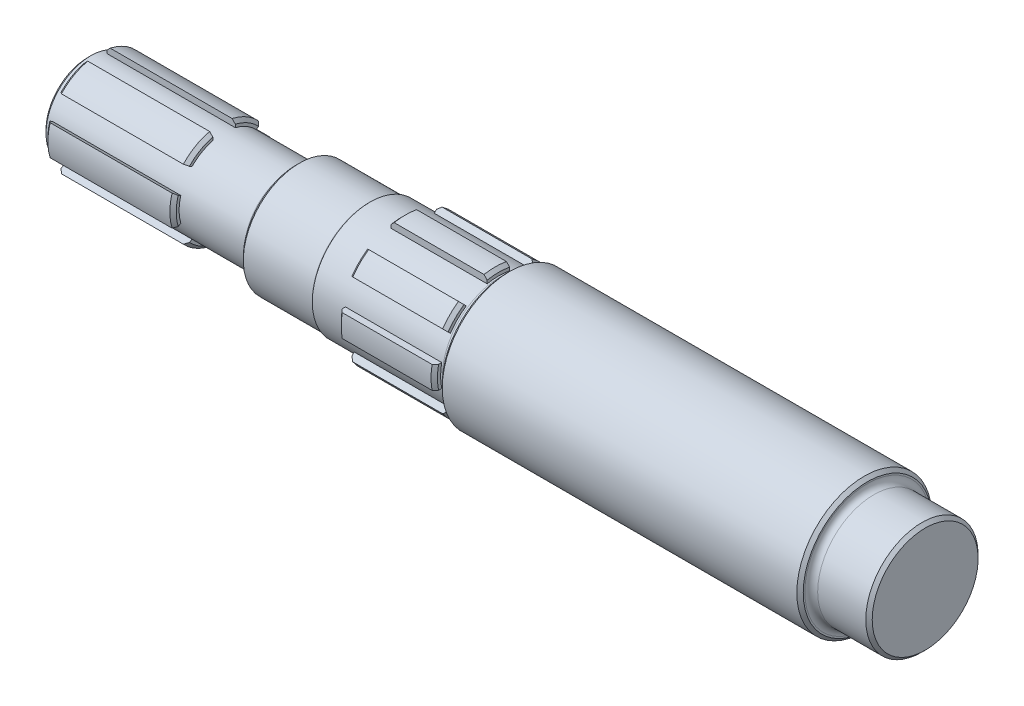
SolidWorks part; units mm, degrees
ref_plane "Front Plane" through (0, 0, 0) normal (0, 0, 1) x (1, 0, 0)
ref_plane "Top Plane" through (0, 0, 0) normal (0, 1, 0) x (1, 0, 0)
ref_plane "Right Plane" through (0, 0, 0) normal (1, 0, 0) x (0, 0, -1)
sketch "Sketch1" plane through (0, 0, 0) normal (0, 0, 1) x (1, 0, 0)
  line L0 (-88.5202, 0) -> (101.5471, 0) construction
  line L1 (-80.5157, 0) -> (-80.5157, 17.5)
  line L2 (-80.5157, 17.5) -> (-57.5157, 17.5)
  line L3 (-57.5157, 17.5) -> (-57.5157, 18)
  line L4 (-57.5157, 18) -> (-47.5157, 18)
  line L5 (-15.0157, 18) -> (-15.0157, 21)
  line L6 (-15.0157, 21) -> (97.4843, 21)
  line L7 (97.4843, 21) -> (97.4843, 17.5)
  line L8 (97.4843, 17.5) -> (115.4843, 17.5)
  line L9 (115.4843, 17.5) -> (115.4843, 0)
  line L10 (-80.5157, 0) -> (115.4843, 0)
  line L11 (-47.5157, 18) -> (-47.5157, 20)
  line L12 (-47.5157, 20) -> (-17.5157, 20)
  line L13 (-17.5157, 20) -> (-17.5157, 18)
  line L14 (-17.5157, 18) -> (-15.0157, 18)
  point P5 (-32.5157, 18)
  dimension "D1" = 17.5
  dimension "D2" = 23
  dimension "D3" = 42.5
  dimension "D4" = 112.5
  dimension "D5" = 18
  dimension "D6" = 21
  dimension "D7" = 17.5
  dimension "D8" = 18
  dimension "D9" = 25
  dimension "D10" = 15
  dimension "D11" = 15
  dimension "D12" = 20
revolve "Revolve1" add sketch "Sketch1" angle 360 about L0
sketch "Sketch2" plane through (-80.5157, 0, 0) normal (-1, 0, 0) x (0, 0, 1)
  circle A2 centre (0, 0) radius 14
  dimension "D1" = 28
extrude "Boss-Extrude1" add sketch "Sketch2" along normal blind 65
sketch "Sketch3" plane through (-47.5157, 0, 0) normal (-1, 0, 0) x (0, 0, 1)
  line L0 (0, 0) -> (0, 24.1209) construction
  line L1 (3.5, 19.6914) -> (3.5, 17.6564)
  line L2 (-3.5, 19.6914) -> (-3.5, 17.6564)
  line L3 (11.449, 16.3988) -> (10.0101, 14.9599)
  line L4 (16.3988, 11.449) -> (14.9599, 10.0101)
  line L5 (19.6914, 3.5) -> (17.6564, 3.5)
  line L6 (19.6914, -3.5) -> (17.6564, -3.5)
  line L7 (16.3988, -11.449) -> (14.9599, -10.0101)
  line L8 (11.449, -16.3988) -> (10.0101, -14.9599)
  line L9 (3.5, -19.6914) -> (3.5, -17.6564)
  line L10 (-3.5, -19.6914) -> (-3.5, -17.6564)
  line L11 (-11.449, -16.3988) -> (-10.0101, -14.9599)
  line L12 (-16.3988, -11.449) -> (-14.9599, -10.0101)
  line L13 (-19.6914, -3.5) -> (-17.6564, -3.5)
  line L14 (-19.6914, 3.5) -> (-17.6564, 3.5)
  line L15 (-16.3988, 11.449) -> (-14.9599, 10.0101)
  line L16 (-11.449, 16.3988) -> (-10.0101, 14.9599)
  circle A3 centre (0, 0) radius 18 construction
  circle A23 centre (0, 0) radius 18 construction
  circle A24 centre (0, 0) radius 20 construction
  arc A25 (-14.9599, 10.0101) -> (-17.6564, 3.5) centre (0, 0) ccw
  arc A26 (-16.3988, 11.449) -> (-19.6914, 3.5) centre (0, 0) ccw
  arc A27 (-19.6914, -3.5) -> (-16.3988, -11.449) centre (0, 0) ccw
  arc A28 (-17.6564, -3.5) -> (-14.9599, -10.0101) centre (0, 0) ccw
  arc A29 (-11.449, -16.3988) -> (-3.5, -19.6914) centre (0, 0) ccw
  arc A30 (-10.0101, -14.9599) -> (-3.5, -17.6564) centre (0, 0) ccw
  arc A31 (3.5, -19.6914) -> (11.449, -16.3988) centre (0, 0) ccw
  arc A32 (3.5, -17.6564) -> (10.0101, -14.9599) centre (0, 0) ccw
  arc A33 (16.3988, -11.449) -> (19.6914, -3.5) centre (0, 0) ccw
  arc A34 (14.9599, -10.0101) -> (17.6564, -3.5) centre (0, 0) ccw
  arc A35 (19.6914, 3.5) -> (16.3988, 11.449) centre (0, 0) ccw
  arc A36 (17.6564, 3.5) -> (14.9599, 10.0101) centre (0, 0) ccw
  arc A37 (11.449, 16.3988) -> (3.5, 19.6914) centre (0, 0) ccw
  arc A38 (10.0101, 14.9599) -> (3.5, 17.6564) centre (0, 0) ccw
  arc A39 (-3.5, 19.6914) -> (-11.449, 16.3988) centre (0, 0) ccw
  arc A40 (-3.5, 17.6564) -> (-10.0101, 14.9599) centre (0, 0) ccw
  point P40 (0, 0)
  dimension "D1" = 8
extrude "Cut-Extrude1" cut sketch "Sketch3" against normal blind 30
fillet "Fillet1" radius 2 1 edges at (-15.0157, 0, 18)
fillet "Fillet2" radius 2 1 edges at (97.4843, 0, 17.5)
fillet "Fillet3" radius 0.5 1 edges at (-57.5157, 0, 17.5)
ref_plane "Plane1" through (-143.0157, 0, 0) normal (-1, 0, 0) x (0, 0, 1)
chamfer "Chamfer1" distance 1 angle 45 16 edges at (-47.5157, -20, 0) (-47.5157, -14.1421, 14.1421) (-47.5157, 0, 20) (-47.5157, -12.7279, -12.7279) (-47.5157, 0, -20) (-47.5157, 14.1421, 14.1421) (-47.5157, 20, 0) (-47.5157, 14.1421, -14.1421) (-17.5157, 20, 0) (-17.5157, 14.1421, 14.1421) (-17.5157, 0, 20) (-17.5157, -14.1421, 14.1421) (-17.5157, -20, 0) (-17.5157, -14.1421, -14.1421) (-17.5157, 0, -20) (-17.5157, 14.1421, -14.1421)
sketch "Sketch6" plane through (-143.0157, 0, 0) normal (-1, 0, 0) x (0, 0, 1)
  line L0 (0, 0) -> (0, 21.7594) construction
  line L1 (-3.5, 13.5554) -> (-3.5, 15.5248)
  line L2 (9.9894, 9.8088) -> (11.6949, 10.7935)
  line L3 (15.1949, 4.7313) -> (13.4894, 3.7466)
  line L4 (3.5, 15.5248) -> (3.5, 13.5554)
  line L5 (13.4894, -3.7466) -> (15.1949, -4.7313)
  line L6 (11.6949, -10.7935) -> (9.9894, -9.8088)
  line L7 (3.5, -13.5554) -> (3.5, -15.5248)
  line L8 (-3.5, -15.5248) -> (-3.5, -13.5554)
  line L9 (-9.9894, -9.8088) -> (-11.6949, -10.7935)
  line L10 (-15.1949, -4.7313) -> (-13.4894, -3.7466)
  line L11 (-13.4894, 3.7466) -> (-15.1949, 4.7313)
  line L12 (-11.6949, 10.7935) -> (-9.9894, 9.8088)
  circle A0 centre (0, 0) radius 14 construction
  arc A1 (-13.4894, 3.7466) -> (-13.4894, -3.7466) centre (0, 0) ccw
  arc A2 (-15.1949, 4.7313) -> (-15.1949, -4.7313) centre (0, 0) ccw
  arc A3 (-3.5, 15.5248) -> (-11.6949, 10.7935) centre (0, 0) ccw
  arc A4 (-3.5, 13.5554) -> (-9.9894, 9.8088) centre (0, 0) ccw
  arc A5 (11.6949, 10.7935) -> (3.5, 15.5248) centre (0, 0) ccw
  arc A6 (9.9894, 9.8088) -> (3.5, 13.5554) centre (0, 0) ccw
  arc A7 (15.1949, -4.7313) -> (15.1949, 4.7313) centre (0, 0) ccw
  arc A8 (13.4894, -3.7466) -> (13.4894, 3.7466) centre (0, 0) ccw
  arc A9 (3.5, -15.5248) -> (11.6949, -10.7935) centre (0, 0) ccw
  arc A10 (3.5, -13.5554) -> (9.9894, -9.8088) centre (0, 0) ccw
  arc A11 (-11.6949, -10.7935) -> (-3.5, -15.5248) centre (0, 0) ccw
  arc A12 (-9.9894, -9.8088) -> (-3.5, -13.5554) centre (0, 0) ccw
  point P31 (0, 0)
  dimension "D1" = 3.5
  dimension "D2" = 3.5
  dimension "D3" = 6
extrude "Boss-Extrude4" add sketch "Sketch6" against normal blind 40
chamfer "Chamfer3" distance 1 angle 45 12 edges at (-103.0157, -13.7823, 7.9572) (-103.0157, 0, 15.9145) (-103.0157, 13.7823, 7.9572) (-103.0157, -13.7823, -7.9572) (-103.0157, 0, -15.9145) (-103.0157, 13.7823, -7.9572) (-143.0157, -13.7823, -7.9572) (-143.0157, 0, -15.9145) (-143.0157, -13.7823, 7.9572) (-143.0157, 0, 15.9145) (-143.0157, 13.7823, -7.9572) (-143.0157, 13.7823, 7.9572)
chamfer "Chamfer4" distance 1 angle 45 1 edges at (-80.5157, 0, 17.5)
fillet "Fillet4" radius 2 1 edges at (-80.5157, 0, 14)
chamfer "Chamfer5" distance 1 angle 45 1 edges at (-15.0157, 0, 21)
chamfer "Chamfer6" distance 1 angle 45 1 edges at (-145.5157, 0, 14)
chamfer "Chamfer7" distance 1 angle 45 1 edges at (97.4843, 0, 21)
chamfer "Chamfer8" distance 1 angle 45 1 edges at (115.4843, 0, 17.5)
